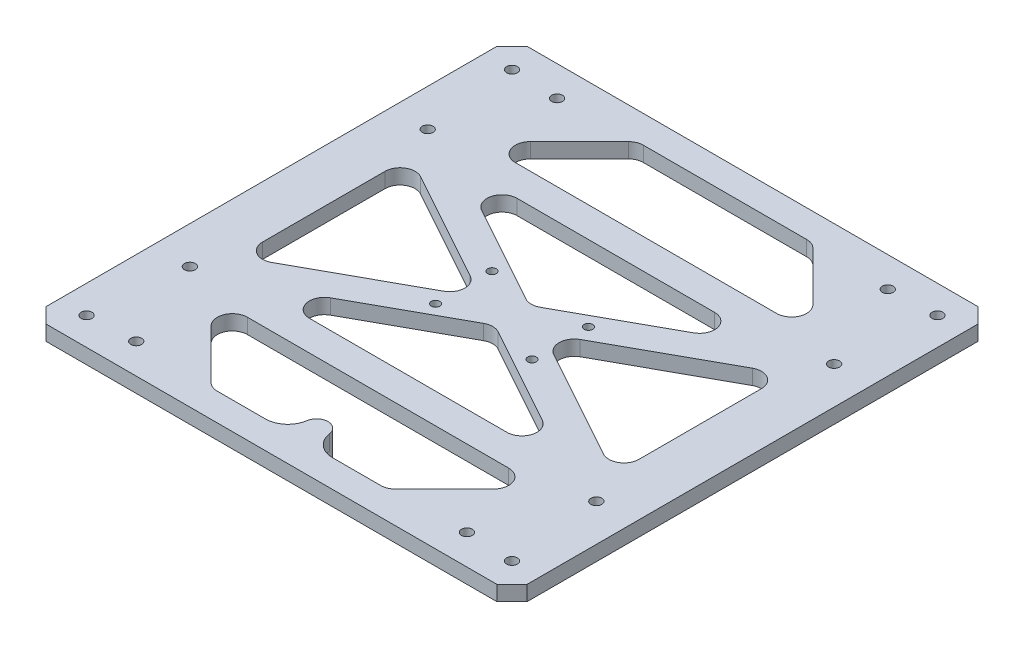
SolidWorks part; units mm, degrees
ref_plane "Front Plane" through (0, 0, 0) normal (0, 0, 1) x (1, 0, 0)
ref_plane "Top Plane" through (0, 0, 0) normal (0, 1, 0) x (1, 0, 0)
ref_plane "Right Plane" through (0, 0, 0) normal (1, 0, 0) x (0, 0, -1)
sketch "Sketch1" plane through (0, 0, 0) normal (0, 1, 0) x (1, 0, 0)
  line L0 (0, 196.85) -> (6.35, 203.2)
  line L1 (6.35, 0) -> (196.85, 0)
  line L2 (0, 6.35) -> (0, 196.85)
  line L3 (6.35, 203.2) -> (196.85, 203.2)
  line L4 (203.2, 6.35) -> (203.2, 196.85)
  line L5 (196.85, 203.2) -> (203.2, 196.85)
  line L6 (196.85, 0) -> (203.2, 6.35)
  line L7 (0, 6.35) -> (6.35, 0)
  point P0 (0, 0)
  point P1 (203.2, 203.2)
  point P2 (0, 203.2)
  point P3 (203.2, 0)
  dimension "D1" = 203.2
  dimension "D2" = 203.2
extrude "Boss-Extrude1" add sketch "Sketch1" along normal blind 6.35
sketch "Sketch3" plane through (0, 6.35, 0) normal (0, 1, 0) x (1, 0, 0)
  line L0 (6.35, 0) -> (196.85, 0) construction
  line L1 (0, 196.85) -> (0, 6.35) construction
  line L2 (203.2, 6.35) -> (203.2, 196.85) construction
  line L3 (196.85, 203.2) -> (6.35, 203.2) construction
  circle A0 centre (11.7373, 11.7373) radius 2.286
  circle A1 centre (191.4627, 11.7373) radius 2.286
  circle A2 centre (191.4627, 191.4627) radius 2.286
  circle A3 centre (11.7373, 191.4627) radius 2.286
  dimension "D1" = 2
  dimension "D3" = 4.572
  dimension "D4" = 11.7373
  dimension "D5" = 11.7373
  dimension "D6" = 11.7373
  dimension "D7" = 11.7373
  dimension "D8" = 11.7373
  dimension "D2" = 2
extrude "Cut-Extrude2" cut sketch "Sketch3" against normal through all
sketch "Sketch4" plane through (0, 6.35, 0) normal (0, 1, 0) x (1, 0, 0)
  line L0 (0, 196.85) -> (0, 6.35) construction
  line L1 (15.748, 151.8285) -> (187.452, 151.8285) construction
  line L2 (15.748, 151.8285) -> (15.748, 51.3715) construction
  line L3 (15.748, 51.3715) -> (187.452, 51.3715) construction
  line L4 (187.452, 151.8285) -> (187.452, 51.3715) construction
  line L5 (196.85, 203.2) -> (6.35, 203.2) construction
  line L6 (12.573, 139.6732) -> (64.4907, 191.591)
  line L7 (138.7093, 191.591) -> (64.4907, 191.591)
  line L8 (138.7093, 191.591) -> (190.627, 139.6732)
  line L9 (190.627, 63.5268) -> (138.7093, 11.609)
  line L10 (190.627, 139.6732) -> (190.627, 63.5268)
  line L11 (138.7093, 11.609) -> (64.4907, 11.609)
  line L12 (64.4907, 11.609) -> (12.573, 63.5268)
  line L13 (12.573, 63.5268) -> (12.573, 139.6732)
  circle A0 centre (15.748, 151.8285) radius 2.286
  circle A1 centre (187.452, 151.8285) radius 2.286
  circle A2 centre (187.452, 51.3715) radius 2.286
  circle A3 centre (15.748, 51.3715) radius 2.286
  point P6 (0, 101.6)
  point P7 (15.748, 101.6)
  point P10 (101.6, 203.2)
  point P11 (101.6, 151.8285)
  dimension "D3" = 4.572
  dimension "D5" = 6.35
  dimension "D7" = 6.35
  dimension "D1" = 171.704
  dimension "D2" = 100.457
  dimension "D4" = 6.35
  dimension "D6" = 6.35
  dimension "D8" = 6.35
extrude "Cut-Extrude3" cut sketch "Sketch4" against normal through all
sketch "Sketch5" plane through (0, 6.35, 0) normal (0, 1, 0) x (1, 0, 0)
  line L0 (15.748, 51.3715) -> (187.452, 51.3715) construction
  line L1 (187.452, 51.3715) -> (187.452, 151.8285) construction
  line L2 (187.452, 151.8285) -> (15.748, 151.8285) construction
  line L3 (15.748, 151.8285) -> (15.748, 51.3715) construction
  line L4 (193.802, 158.1785) -> (9.398, 158.1785)
  line L5 (9.398, 158.1785) -> (9.398, 45.0215)
  line L6 (9.398, 45.0215) -> (193.802, 45.0215)
  line L7 (193.802, 45.0215) -> (193.802, 158.1785)
  line L8 (143.3139, 145.4785) -> (59.8861, 145.4785)
  line L9 (22.098, 127.4679) -> (22.098, 75.7321)
  line L10 (59.8861, 57.7215) -> (143.3139, 57.7215)
  line L11 (181.102, 75.7321) -> (181.102, 127.4679)
  line L12 (22.098, 57.7215) -> (181.102, 145.4785) construction
  line L13 (181.102, 57.7215) -> (22.098, 145.4785) construction
  line L14 (56.8177, 69.631) -> (98.5316, 92.6536)
  line L15 (171.6836, 70.1726) -> (124.8144, 96.0405)
  line L16 (31.5164, 70.1726) -> (78.3856, 96.0405)
  line L17 (146.3823, 69.631) -> (104.6684, 92.6536)
  line L18 (184.1704, 63.281) -> (25.1664, 151.038) construction
  line L19 (178.0336, 52.162) -> (19.0296, 139.919) construction
  line L20 (19.0296, 63.281) -> (178.0336, 151.038) construction
  line L21 (25.1664, 52.162) -> (184.1704, 139.919) construction
  line L22 (22.098, 57.7215) -> (181.102, 57.7215) construction
  line L23 (181.102, 57.7215) -> (181.102, 145.4785) construction
  line L24 (181.102, 145.4785) -> (22.098, 145.4785) construction
  line L25 (22.098, 145.4785) -> (22.098, 57.7215) construction
  line L26 (78.3856, 107.1595) -> (31.5164, 133.0274)
  line L27 (104.6684, 110.5464) -> (146.3823, 133.569)
  line L28 (124.8144, 107.1595) -> (171.6836, 133.0274)
  line L29 (98.5316, 110.5464) -> (56.8177, 133.569)
  circle A0 centre (187.452, 51.3715) radius 2.286 construction
  circle A1 centre (187.452, 151.8285) radius 2.286 construction
  circle A2 centre (15.748, 151.8285) radius 2.286 construction
  circle A3 centre (15.748, 51.3715) radius 2.286 construction
  circle A4 centre (187.452, 51.3715) radius 2.286
  circle A5 centre (187.452, 151.8285) radius 2.286
  circle A6 centre (15.748, 151.8285) radius 2.286
  circle A7 centre (15.748, 51.3715) radius 2.286
  arc A8 (56.8177, 133.569) -> (59.8861, 145.4785) centre (59.8861, 139.1285) cw
  arc A9 (146.3823, 133.569) -> (143.3139, 145.4785) centre (143.3139, 139.1285) ccw
  arc A10 (171.6836, 133.0274) -> (181.102, 127.4679) centre (174.752, 127.4679) cw
  arc A11 (124.8144, 107.1595) -> (124.8144, 96.0405) centre (127.8827, 101.6) ccw
  arc A12 (171.6836, 70.1726) -> (181.102, 75.7321) centre (174.752, 75.7321) ccw
  arc A13 (146.3823, 69.631) -> (143.3139, 57.7215) centre (143.3139, 64.0715) cw
  arc A14 (104.6684, 92.6536) -> (98.5316, 92.6536) centre (101.6, 87.0941) ccw
  arc A15 (78.3856, 107.1595) -> (78.3856, 96.0405) centre (75.3173, 101.6) cw
  arc A16 (31.5164, 133.0274) -> (22.098, 127.4679) centre (28.448, 127.4679) ccw
  arc A17 (31.5164, 70.1726) -> (22.098, 75.7321) centre (28.448, 75.7321) cw
  arc A18 (56.8177, 69.631) -> (59.8861, 57.7215) centre (59.8861, 64.0715) ccw
  arc A19 (98.5316, 110.5464) -> (104.6684, 110.5464) centre (101.6, 116.1059) ccw
  dimension "D5" = 6.35
  dimension "D6" = 6.35
  dimension "D1" = 6.35
  dimension "D3" = 6.35
  dimension "D2" = 6.35
  dimension "D4" = 6.35
extrude "Boss-Extrude2" add sketch "Sketch5" against normal up to surface (6.35 mm away) up to face at (187.452, 0, -149.5425)
fillet "Fillet1" radius 6.35 8 edges at (138.7093, 3.175, -191.591) (64.4907, 3.175, -191.591) (31.0783, 3.175, -158.1785) (172.1217, 3.175, -158.1785) (64.4907, 3.175, -11.609) (31.0783, 3.175, -45.0215) (138.7093, 3.175, -11.609) (172.1217, 3.175, -45.0215)
sketch "Sketch6" plane through (0, 6.35, 0) normal (0, 1, 0) x (1, 0, 0)
  line L0 (6.35, 0) -> (196.85, 0) construction
  line L1 (67.121, 11.609) -> (136.079, 11.609) construction
  line L2 (87.4011, 11.609) -> (115.7989, 11.609)
  circle A0 centre (101.6, 19.05) radius 2.286 construction
  arc A1 (106.3748, 19.7508) -> (96.8252, 19.7508) centre (101.6, 19.05) ccw
  arc A2 (87.4011, 11.609) -> (96.8252, 19.7508) centre (87.4011, 21.134) ccw
  arc A3 (106.3748, 19.7508) -> (115.7989, 11.609) centre (115.7989, 21.134) ccw
  point P7 (101.6, 0)
  dimension "D1" = 19.05
  dimension "D2" = 4.572
  dimension "D3" = 2.54
  dimension "D4" = 19.05
extrude "Boss-Extrude3" add sketch "Sketch6" against normal up to surface (6.35 mm away) up to face at (101.6, 0, -26.3336)
sketch "Sketch8" plane through (0, 0, 0) normal (0, 1, 0) x (1, 0, 0)
  circle A0 centre (101.6, 19.05) radius 4.826
  circle A1 centre (101.6, 19.05) radius 2.286
  arc A2 (106.3748, 19.7508) -> (96.8252, 19.7508) centre (101.6, 19.05) ccw construction
  dimension "D1" = 4.572
extrude "Boss-Extrude4" add sketch "Sketch8" against normal blind 6.35
sketch "Sketch9" plane through (0, 0, 0) normal (0, 1, 0) x (1, 0, 0)
  line L0 (79.6765, 114.4265) -> (123.5235, 88.7735) construction
  line L1 (123.5235, 114.4265) -> (79.6765, 88.7735) construction
  circle A0 centre (121.9669, 113.5159) radius 1.8034 construction
  circle A1 centre (81.2331, 113.5159) radius 1.8034 construction
  circle A2 centre (81.2331, 89.6841) radius 1.8034 construction
  circle A3 centre (121.9669, 89.6841) radius 1.8034 construction
  circle A4 centre (81.2331, 113.5159) radius 3.8354
  circle A5 centre (121.9669, 113.5159) radius 3.8354
  circle A6 centre (121.9669, 89.6841) radius 3.8354
  circle A7 centre (81.2331, 89.6841) radius 3.8354
  point P8 (101.6, 101.6)
  dimension "D1" = 3.6068
  dimension "D2" = 50.8
  dimension "D3" = 119.34
  dimension "D4" = 2.032
extrude "Cut-Extrude4" cut sketch "Sketch9" along normal offset from surface (3.81 mm away) 2.54 up to face at (101.6, 6.35, -22.8339)
sketch "Sketch10" plane through (0, 3.81, 0) normal (0, -1, 0) x (-1, 0, 0)
  circle A26 centre (-81.2331, 113.5159) radius 1.8034
  circle A27 centre (-121.9669, 113.5159) radius 1.8034
  circle A28 centre (-121.9669, 89.6841) radius 1.8034
  circle A29 centre (-81.2331, 89.6841) radius 1.8034
  dimension "D1" = 3.6068
extrude "Cut-Extrude5" cut sketch "Sketch10" against normal through all
sketch "Sketch11" plane through (0, 0, 0) normal (0, -1, 0) x (1, 0, 0)
  line L0 (0, -196.85) -> (0, -6.35) construction
  line L1 (6.35, 0) -> (196.85, 0) construction
  line L2 (196.85, -203.2) -> (6.35, -203.2) construction
  line L3 (203.2, -6.35) -> (203.2, -196.85) construction
  circle A0 centre (31.75, -12.7) radius 2.286
  circle A1 centre (171.45, -12.7) radius 2.286
  circle A2 centre (171.45, -190.5) radius 2.286
  circle A3 centre (31.75, -190.5) radius 2.286
  dimension "D1" = 4.572
  dimension "D6" = 12.7
  dimension "D7" = 31.75
  dimension "D8" = 31.75
  dimension "D2" = 31.75
  dimension "D3" = 12.7
  dimension "D4" = 2
  dimension "D5" = 2
extrude "Cut-Extrude6" cut sketch "Sketch11" against normal through all and the other way through all
